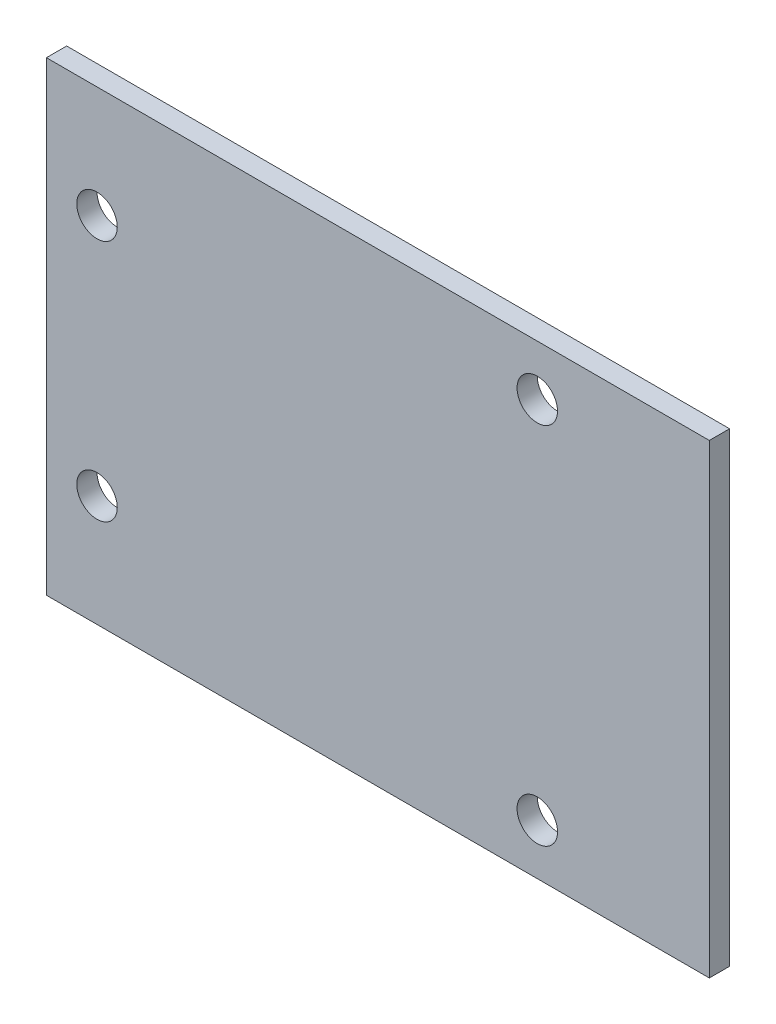
SolidWorks part; units mm, degrees
ref_plane "Plan de face" through (0, 0, 0) normal (0, 0, 1) x (1, 0, 0)
ref_plane "Plan de dessus" through (0, 0, 0) normal (0, 1, 0) x (1, 0, 0)
ref_plane "Plan de droite" through (0, 0, 0) normal (1, 0, 0) x (0, 0, -1)
sketch "Esquisse1" plane through (0, 0, 0) normal (0, 0, 1) x (1, 0, 0)
  line L1 (0, 0) -> (65.5, 0)
  line L2 (0, 0) -> (0, 46)
  line L3 (0, 46) -> (65.5, 46)
  line L4 (65.5, 0) -> (65.5, 46)
  dimension "D1" = 46
  dimension "D2" = 65.5
extrude "Boss.-Extru.1" add sketch "Esquisse1" along normal blind 2
sketch "Esquisse2" plane through (0, 0, 2) normal (0, 0, 1) x (1, 0, 0)
  line L1 (0, 0) -> (65.5, 0) construction
  line L2 (65.5, 46) -> (0, 46) construction
  line L3 (0, 46) -> (0, 0) construction
  circle A0 centre (5, 11) radius 2
  circle A1 centre (5, 35) radius 2
  circle A2 centre (48.5, 41) radius 2
  circle A3 centre (48.5, 5) radius 2
  point P8 (0, 0)
  point P13 (0, 0)
  point P14 (0, 0)
  point P15 (0, 0)
  dimension "D1" = 4
  dimension "D2" = 48.5
  dimension "D3" = 5
  dimension "D4" = 11
  dimension "D5" = 11
  dimension "D6" = 5
  dimension "D7" = 5
extrude "Enlèv. mat.-Extru.1" cut sketch "Esquisse2" against normal through all
